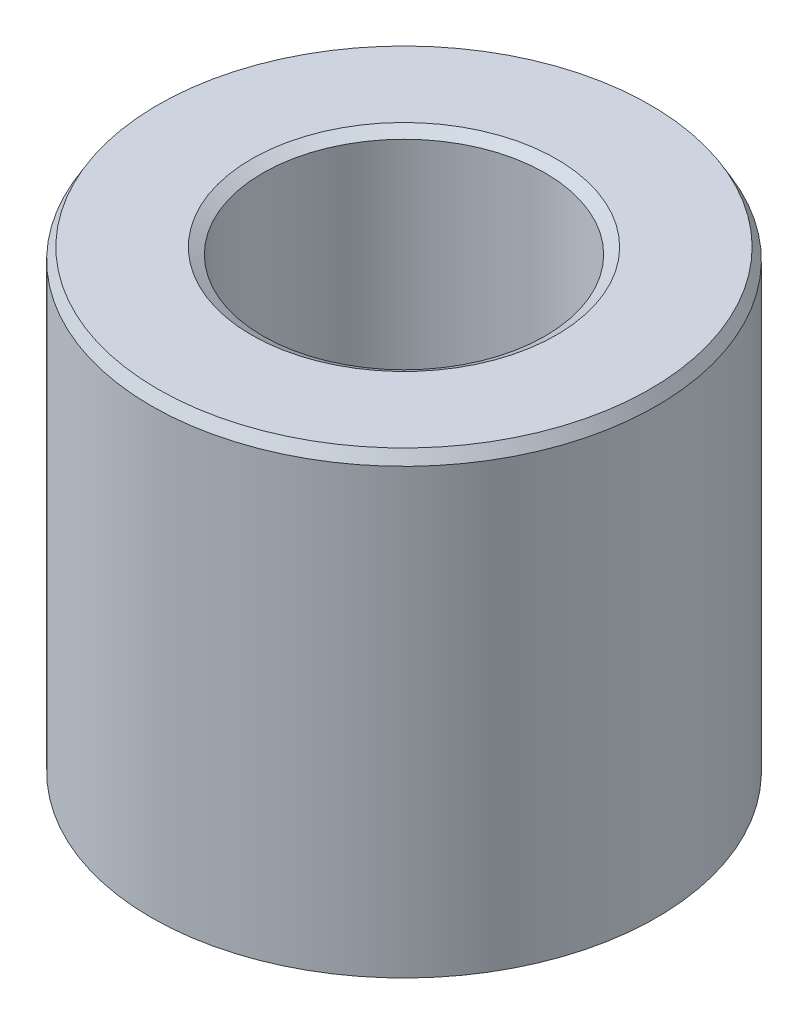
SolidWorks part; units mm, degrees
ref_plane "Front Plane" through (0, 0, 0) normal (0, 0, 1) x (1, 0, 0)
ref_plane "Top Plane" through (0, 0, 0) normal (0, 1, 0) x (1, 0, 0)
ref_plane "Right Plane" through (0, 0, 0) normal (1, 0, 0) x (0, 0, -1)
sketch "Sketch1" plane through (0, 0, 0) normal (0, 1, 0) x (1, 0, 0)
  circle A0 centre (0, 0) radius 42.5
  dimension "SLEEVE_OD" = 85
extrude "Boss-Extrude1" add sketch "Sketch1" along normal blind 77.5242
sketch "Sketch2" plane through (0, 0, 0) normal (0, 1, 0) x (1, 0, 0)
  circle A0 centre (0, 0) radius 23.7478
  dimension "BORE_D" = 47.4957
extrude "Cut-Extrude1" cut sketch "Sketch2" along normal through all
chamfer "Chamfer1" distance 1.9002 angle 30 4 edges at (0, 77.5242, 23.7478) (0, 0, 23.7478) (0, 0, 42.5) (0, 77.5242, 42.5) first distance on face at (0, 77.5242, 23.7478) first distance on face at (0, 0, 23.7478) first distance on face at (0, 77.5242, 42.5)
